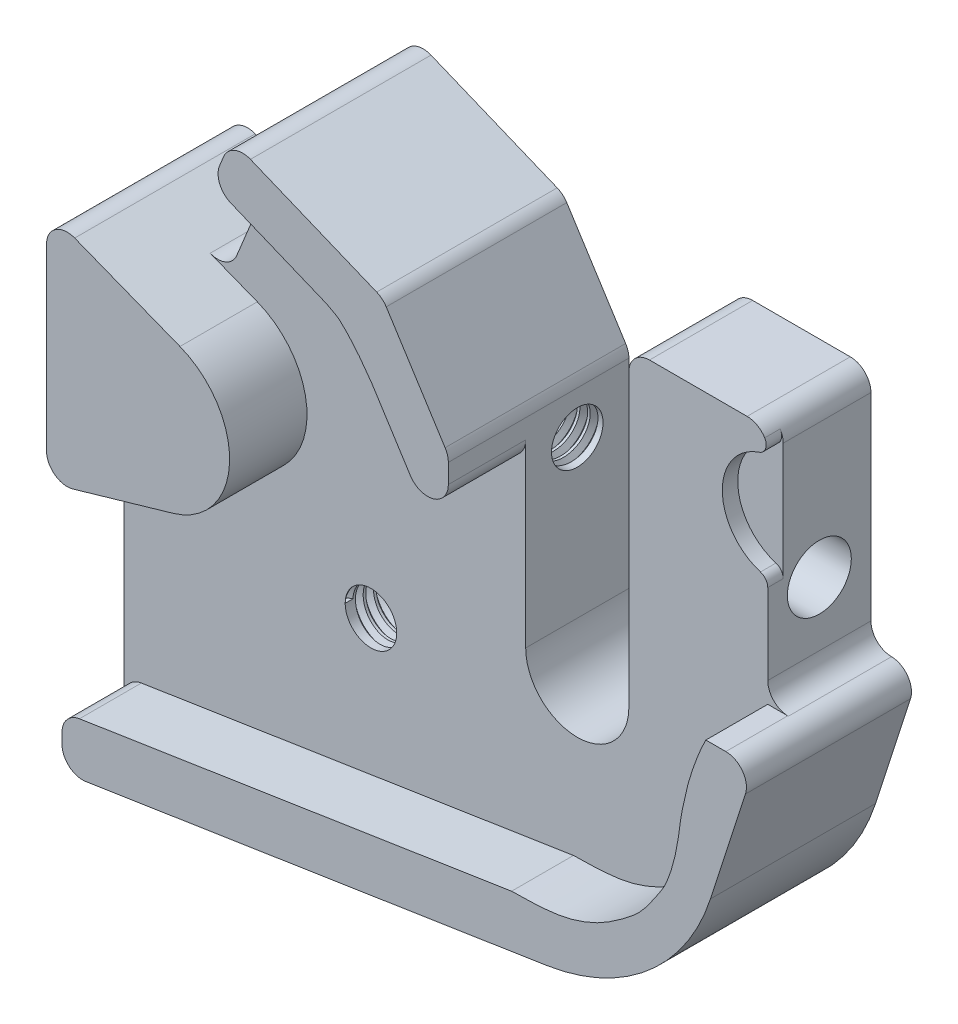
SolidWorks part; units mm, degrees
ref_plane "Front Plane" through (0, 0, 0) normal (0, 0, 1) x (1, 0, 0)
ref_plane "Top Plane" through (0, 0, 0) normal (0, 1, 0) x (1, 0, 0)
ref_plane "Right Plane" through (0, 0, 0) normal (1, 0, 0) x (0, 0, -1)
sketch "Sketch1" plane through (0, 0, 0) normal (0, 0, 1) x (1, 0, 0)
  line L0 (169.0465, 531.5792) -> (1384.9618, 942.3347) construction
  line L1 (17.1755, 0.269) -> (145.8355, -18.3486) construction
  line L2 (78.9683, 43.5936) -> (88.9683, 43.5936)
  line L3 (88.9683, 43.5936) -> (88.9683, 26.5936)
  line L4 (88.9683, 26.5936) -> (78.9683, 26.5936)
  line L5 (78.9683, 26.5936) -> (78.9683, 43.5936)
  line L6 (77.9414, 43.8024) -> (71.5407, 53.8656)
  line L7 (56.0381, 62.9033) -> (67.1668, 58.333)
  line L8 (88.9683, 43.5936) -> (88.9683, 61.7655)
  line L9 (88.9683, 61.7655) -> (102.4319, 61.7655)
  line L10 (77.9414, 43.8024) -> (78.9683, 42.1878)
  line L11 (20.6229, 24.1202) -> (53.1029, 33.5417)
  line L12 (23.9133, 59.0209) -> (55.1963, 46.7648)
  line L13 (56.0381, 62.9033) -> (50.2123, 48.7174)
  line L14 (70.3698, 62.4229) -> (72.6084, 61.5036)
  line L15 (20.6228, 1.7046) -> (20.6229, 24.1202)
  line L16 (20.6229, 24.1202) -> (20.6229, 30.1202)
  line L17 (103.2745, 61.7655) -> (102.4319, 61.7655)
  line L18 (20.6229, 30.1202) -> (43.6301, 36.7939)
  line L19 (23.9133, 59.0209) -> (22.0894, 54.3655)
  line L20 (22.0894, 54.3655) -> (44.4958, 45.587)
  line L21 (78.9683, 43.5936) -> (78.9683, 49.4415)
  line L22 (57.9376, 67.5285) -> (70.3698, 62.4229)
  line L23 (83.9683, 38.5936) -> (107.1142, 38.5936)
  line L24 (40.0198, 35.7467) -> (40.0198, 47.3406)
  line L25 (40.0198, 47.3406) -> (40.0198, 52.7107)
  line L26 (56.0381, 62.9033) -> (57.9376, 67.5285)
  line L27 (103.4635, 40.5809) -> (107.7563, 40.5809) construction
  line L28 (40.0198, 35.7467) -> (40.0198, 4.6997)
  line L29 (107.7563, 40.5809) -> (99.1103, 13.8239)
  line L30 (102.4319, 61.7655) -> (102.4319, 40.5809)
  line L31 (99.1103, 13.8239) -> (20.6228, 1.7046)
  line L32 (83.9683, 43.5936) -> (83.9683, 46.6936)
  line L33 (20.6228, 6.4639) -> (20.6228, 6.7639)
  line L34 (20.6228, 6.7639) -> (83.6, 16.4882)
  line L35 (20.6229, 30.1202) -> (20.6229, 61.7655)
  line L36 (23.9133, 59.0209) -> (20.6229, 60.3101)
  line L37 (22.0894, 54.3655) -> (20.6229, 54.94)
  line L38 (73.7743, 50.3539) -> (77.9932, 53.0374) construction
  line L39 (77.9932, 53.0374) -> (71.1704, 63.7644)
  line L40 (77.9932, 53.0374) -> (78.9683, 51.5043)
  line L41 (78.9683, 51.5043) -> (78.9683, 49.4415)
  line L42 (102.4319, 40.5809) -> (102.4319, 38.5936)
  line L47 (102.4319, 40.5809) -> (103.4635, 40.5809) construction
  circle A0 centre (83.9683, 31.5936) radius 5
  circle A1 centre (83.9683, 38.5936) radius 5
  circle A5 centre (50.1903, 40.5872) radius 7.578
  circle A6 centre (103.2745, 54.3655) radius 4.4
  circle A7 centre (103.2745, 54.3655) radius 7.4
  circle A8 centre (83.9683, 31.5936) radius 19.8723
  spline S0 degree 3 poles (67.1668, 58.333) (67.5307, 58.1482) (68.2163, 57.8297) (69.7375, 56.3376) (70.7671, 54.998) (71.5407, 53.8656) knots 0 0 0 0 0.194176 0.353383 1 1 1 1
  spline S1 degree 3 poles (83.6, 16.4882) (85.4172, 16.5376) (87.878, 16.5192) (90.6726, 17.4205) (92.3949, 18.1773) (94.0998, 19.3373) (95.7619, 20.5842) (96.8381, 21.8934) (97.5722, 23.0215) (98.2993, 24.0127) (98.8168, 25.1807) (99.3382, 26.7948) (99.7545, 28.7331) (99.9792, 30.8782) (100.4112, 32.873) (100.8434, 34.6928) (101.4168, 36.2088) (101.8572, 37.4461) (102.3579, 38.4137) (102.8415, 39.4999) (103.165, 40.2018) (103.4635, 40.5809) knots 0 0 0 0 0.157684 0.206761 0.251698 0.319001 0.383658 0.429514 0.463788 0.499543 0.534878 0.573031 0.645405 0.704849 0.75836 0.820852 0.865423 0.897677 0.933689 0.958942 1 1 1 1
  spline S2 degree 3 poles (103.4635, 40.5809) (103.5281, 40.7021) (103.6539, 40.9177) (103.7777, 41.1891) (104.0324, 41.5752) (104.2845, 42.0418) (104.6133, 42.6639) (105.0506, 43.3284) (105.5376, 44.1633) (106.1189, 44.9679) (106.7473, 45.8247) (107.3304, 46.576) (107.8594, 47.2965) (108.3783, 47.8664) (108.8492, 48.4246) (109.2415, 48.9281) (109.5877, 49.4941) (110.1609, 50.7988) (110.3782, 52.0409) (110.5419, 52.9707) knots 0 0 0 0 0.032133 0.040138 0.080049 0.114202 0.15475 0.224504 0.279876 0.355143 0.430433 0.500504 0.552615 0.615873 0.660356 0.704255 0.748281 0.797656 1 1 1 1
  dimension "D7" = 5
  dimension "D5" = 8.8
  dimension "D6" = 14.8
  dimension "D1" = 130
  dimension "D2" = 10
  dimension "D3" = 17
  dimension "D4" = 81.222
  dimension "D8" = 5
  dimension "D9" = 5
  dimension "D10" = 5
extrude "Main body" add sketch "Sketch1" along normal blind 10 contours L34 S1 A8 L47 L30 L8 L3 L4 L5 L10 L6 | S0 L7 L13 L12 A5 L11 L28 L34 A8 L6 | A0 L5 L4 | A0 L4 L3 | A8 L30 A7 L9 L8 | L30 A7 | L30 A8 L8 L3 L23 L42 | L30 A6 region at (78.4544, 40.3907, 0) region at (94.2116, 43.3445, 0) region at (94.7009, 53.6895, 0) region at (87.8514, 27.7104, 0) region at (80.0851, 27.7104, 0) region at (56.8317, 32.873, 0) region at (102.2709, 60.2007, 0) region at (100.9442, 54.3655, 0)
extrude "Top brackets" add sketch "Sketch1<3>" along normal blind 17.5 contours L7 S0 L6 A8 L41 L40 L39 L14 L22 L26 | L41 A8 L6 L10 L5 L21 | A5 | A5 L12 L25 L20 | A5 L20 L24 L18 | A5 L18 L28 L11 region at (77.485, 47.4328, 0) region at (68.2303, 59.1792, 0) region at (43.4702, 33.1986, 0) region at (43.8977, 48.9301, 0) region at (50.1903, 40.5872, 0) region at (41.5617, 41.668, 0)
sketch "Sketch1<3>" plane through (0, 0, 0) normal (0, 0, 1) x (1, 0, 0) same geometry as "Sketch1"
extrude "Bottom bracket" add sketch "Sketch1<4>" along normal blind 16 contours A8 L29 L23 | S1 L34 A8 L23 | A8 L34 L28 L31 region at (102.4994, 38.1861, 0) region at (104.6837, 35.2862, 0) region at (58.9948, 10.0364, 0)
sketch "Sketch1<4>" plane through (0, 0, 0) normal (0, 0, 1) x (1, 0, 0) same geometry as "Sketch1"
sketch "Sketch4" plane through (88.9683, 0, 0) normal (-1, 0, 0) x (0, 0, 1)
  line L0 (5, 61.7655) -> (5, 46.7655)
  line L2 (10, 61.7655) -> (0, 61.7655) construction
  circle A0 centre (5, 46.7655) radius 3.1
  dimension "D1" = 15
  dimension "D2" = 6.2
extrude "M6 axle tightening hole" cut sketch "Sketch4" against normal blind 30 contours A0 region at (88.9683, 44.6354, 2.87)
hole_wizard "M6 axle tightening tap" positions "3DSketch7" profile "Sketch10" hole size "M6x1.0" standard "ANSI Metric"
sketch3d "3DSketch7"
  line L0 (102.4319, 46.7655, 5) -> (88.9683, 46.7655, 5) construction
  point P0 (88.9683, 46.7655, 5)
sketch "Sketch10" plane through (88.9683, 46.7655, 5) normal (0, 1, 0) x (0, 0, -1)
  line L0 (0, 0) -> (0, 31.5022)
  line L1 (0, 31.5022) -> (2.5, 30)
  line L2 (2.5, 30) -> (2.5, 0)
  line L5 (2.5, 0) -> (0, 0)
  line L10 (0, 31.5022) -> (-2.5, 30) construction
  line L11 (0, -6.35) -> (0, 107.95) construction
  dimension "Hole Dia." = 5
  dimension "Hole Depth" = 30
  dimension "Drill Angle" = 118
thread "M6 axle tightening thread" pitch 1 method cut profile "Thread Profile2" start angle 0, offset 0, length 20, pitch 1, diameter 5
ref_plane "Plane2" through (78.9683, 46.7655, 7.5) normal (0, -1, 0) x (0, 0, 1)
sketch "Thread Profile2" plane through (78.9683, 46.7655, 7.5) normal (0, -1, 0) x (0, 0, 1)
  line L0 (0, 0) -> (0, 1) construction
  line L1 (0, 0) -> (0.5413, 0.3125)
  line L2 (0.5413, 0.3125) -> (0.5413, 0.4375)
  line L3 (0.5413, 0.4375) -> (0, 0.75)
  line L4 (0.5413, 0.375) -> (0, 0.375) construction
  line L11 (0, 0) -> (0, 0.75)
  point P2 (0, 0)
  dimension "Pitch" = 1
  dimension "Profile_Angle" = 60
  dimension "Profile_Land" = 0.125
  dimension "Profile_Height" = 0.5413
sketch "Frame lock position" plane through (0, 0, 10) normal (0, 0, 1) x (1, 0, 0)
  line L0 (83.9683, 26.5936) -> (63.9683, 26.5936)
  arc A0 (78.9683, 31.5936) -> (88.9683, 31.5936) centre (83.9683, 31.5936) ccw construction
hole_wizard "Frame lock tap" positions "3DSketch11" profile "Sketch15" hole size "M6x1.0" standard "ANSI Metric"
sketch3d "3DSketch11"
  point P0 (63.9683, 26.5936, 10)
sketch "Sketch15" plane through (63.9683, 26.5936, 10) normal (1, 0, 0) x (0, -1, 0)
  line L0 (0, 0) -> (0, 31.5022)
  line L1 (0, 31.5022) -> (2.5, 30)
  line L2 (2.5, 30) -> (2.5, 0)
  line L5 (2.5, 0) -> (0, 0)
  line L10 (0, 31.5022) -> (-2.5, 30) construction
  line L11 (0, -6.35) -> (0, 107.95) construction
  dimension "Hole Dia." = 5
  dimension "Hole Depth" = 30
  dimension "Drill Angle" = 118
thread "Frame lock thread" pitch 1 method cut profile "Thread Profile3" start angle 0, offset 0, length 20, pitch 1, diameter 5
ref_plane "Plane3" through (61.4683, 26.5936, 10) normal (0, -1, 0) x (-1, 0, 0)
sketch "Thread Profile3" plane through (61.4683, 26.5936, 10) normal (0, -1, 0) x (-1, 0, 0)
  line L0 (0, 0) -> (0, 1) construction
  line L1 (0, 0) -> (0.5413, 0.3125)
  line L2 (0.5413, 0.3125) -> (0.5413, 0.4375)
  line L3 (0.5413, 0.4375) -> (0, 0.75)
  line L4 (0.5413, 0.375) -> (0, 0.375) construction
  line L11 (0, 0) -> (0, 0.75)
  point P2 (0, 0)
  dimension "Pitch" = 1
  dimension "Profile_Angle" = 60
  dimension "Profile_Land" = 0.125
  dimension "Profile_Height" = 0.5413
fillet "2mm main fillets" radius 2 13 edges at (102.4319, 61.7655, 5) (88.9683, 61.7655, 5) (57.9376, 67.5285, 8.75) (56.0381, 62.9033, 13.75) (78.9683, 42.1878, 13.75) (50.2123, 48.7174, 5) (40.0198, 29.7467, 13.75) (40.0198, 52.7107, 8.75) (72.6084, 61.5036, 8.75) (40.0198, 4.6997, 8) (40.0198, 9.759, 13) (102.4319, 38.5936, 5) (78.9683, 51.5043, 8.75)
fillet "2mm extra fillet" radius 2 1 edges at (107.1142, 38.5936, 8)
sketch "Sketch16" plane through (0, 0, 10) normal (0, 0, 1) x (1, 0, 0)
  line L0 (78.9683, 43.5936) -> (88.9683, 43.5936)
  line L1 (88.9683, 43.5936) -> (88.9683, 26.5936)
  line L2 (88.9683, 26.5936) -> (78.9683, 26.5936)
  line L3 (78.9683, 26.5936) -> (78.9683, 43.5936)
  line L4 (77.9414, 43.8024) -> (71.5407, 53.8656)
  line L5 (56.0381, 62.9033) -> (67.1668, 58.333)
  line L6 (88.9683, 43.5936) -> (88.9683, 61.7655)
  line L7 (88.9683, 61.7655) -> (102.4319, 61.7655)
  line L8 (77.9414, 43.8024) -> (78.9683, 42.1878)
  line L9 (20.6229, 24.1202) -> (53.1029, 33.5417)
  line L10 (23.9133, 59.0209) -> (55.1963, 46.7648)
  line L11 (56.0381, 62.9033) -> (50.2123, 48.7174)
  line L12 (70.5008, 62.7543) -> (72.231, 62.0968)
  line L13 (20.6228, 1.7639) -> (20.6229, 24.1202)
  line L14 (20.6229, 24.1202) -> (20.6229, 30.1202)
  line L15 (103.2745, 61.7655) -> (102.4319, 61.7655)
  line L16 (20.6229, 30.1202) -> (43.6301, 36.7939)
  line L17 (23.9133, 59.0209) -> (22.0894, 54.3655)
  line L18 (22.0894, 54.3655) -> (44.4958, 45.587)
  line L19 (78.9683, 43.5936) -> (78.9683, 49.4415)
  line L20 (57.9376, 67.5285) -> (70.5008, 62.7543)
  line L21 (83.9683, 38.5936) -> (107.6777, 38.5936)
  line L22 (40.0198, 35.7467) -> (40.0198, 47.3406)
  line L23 (40.0198, 47.3406) -> (40.0198, 52.7107)
  line L24 (56.0381, 62.9033) -> (57.9376, 67.5285)
  line L25 (103.4635, 40.5809) -> (108.336, 40.5809) construction
  line L26 (40.0198, 35.7467) -> (40.0198, 4.6135)
  line L27 (108.336, 40.5809) -> (99.307, 13.3233)
  line L28 (102.4319, 61.7655) -> (102.4319, 40.5809)
  line L29 (99.307, 13.3233) -> (20.6228, 1.7639)
  line L30 (83.9683, 43.5936) -> (83.9683, 46.6936)
  line L31 (20.6228, 6.4639) -> (20.6228, 6.7639)
  line L32 (20.6228, 6.7639) -> (83.6, 16.4882)
  line L33 (20.6229, 30.1202) -> (20.6229, 61.7655)
  line L34 (23.9133, 59.0209) -> (20.6229, 60.3101)
  line L35 (22.0894, 54.3655) -> (20.6229, 54.94)
  line L36 (73.7743, 50.3539) -> (77.9932, 53.0374) construction
  line L37 (77.9932, 53.0374) -> (71.1704, 63.7644)
  line L38 (77.9932, 53.0374) -> (78.9683, 51.5043)
  line L39 (78.9683, 51.5043) -> (78.9683, 49.4415)
  line L40 (102.4319, 40.5809) -> (102.4319, 38.5936)
  line L41 (102.4319, 40.5809) -> (103.4635, 40.5809) construction
  circle A0 centre (83.9683, 31.5936) radius 5
  circle A1 centre (83.9683, 38.5936) radius 5
  circle A2 centre (50.1903, 40.5872) radius 7.578
  circle A3 centre (103.2745, 54.3655) radius 4.4
  circle A4 centre (103.2745, 54.3655) radius 7.4
  circle A5 centre (83.9683, 31.5936) radius 20.3057
  circle A6 centre (103.2745, 54.3655) radius 5.25
  spline S0 degree 3 poles (67.1668, 58.333) (67.5307, 58.1482) (68.2163, 57.8297) (69.7375, 56.3376) (70.7671, 54.998) (71.5407, 53.8656) knots 0 0 0 0 0.194176 0.353383 1 1 1 1
  spline S1 degree 3 poles (83.6, 16.4882) (85.4172, 16.5376) (87.878, 16.5192) (90.6726, 17.4205) (92.3949, 18.1773) (94.0998, 19.3373) (95.7619, 20.5842) (96.8381, 21.8934) (97.5722, 23.0215) (98.2993, 24.0127) (98.8168, 25.1807) (99.3382, 26.7948) (99.7545, 28.7331) (99.9792, 30.8782) (100.4112, 32.873) (100.8434, 34.6928) (101.4168, 36.2088) (101.8572, 37.4461) (102.3579, 38.4137) (102.8415, 39.4999) (103.165, 40.2018) (103.4635, 40.5809) knots 0 0 0 0 0.157684 0.206761 0.251698 0.319001 0.383658 0.429514 0.463788 0.499543 0.534878 0.573031 0.645405 0.704849 0.75836 0.820852 0.865423 0.897677 0.933689 0.958942 1 1 1 1
  spline S2 degree 3 poles (103.4635, 40.5809) (103.5281, 40.7021) (103.6539, 40.9177) (103.7777, 41.1891) (104.0324, 41.5752) (104.2845, 42.0418) (104.6133, 42.6639) (105.0506, 43.3284) (105.5376, 44.1633) (106.1189, 44.9679) (106.7473, 45.8247) (107.3304, 46.576) (107.8594, 47.2965) (108.3783, 47.8664) (108.8492, 48.4246) (109.2415, 48.9281) (109.5877, 49.4941) (110.1609, 50.7988) (110.3782, 52.0409) (110.5419, 52.9707) knots 0 0 0 0 0.032133 0.040138 0.080049 0.114202 0.15475 0.224504 0.279876 0.355143 0.430433 0.500504 0.552615 0.615873 0.660356 0.704255 0.748281 0.797656 1 1 1 1
  dimension "D3" = 8.8
  dimension "D4" = 14.8
  dimension "D9" = 10.5
  dimension "D1" = 10
  dimension "D2" = 17
  dimension "D5" = 5
  dimension "D6" = 5
  dimension "D7" = 5
  dimension "D8" = 5
extrude "Derailleur screw cutout" cut sketch "Sketch16" against normal blind 1.5 contours A6
fillet "1mm fillets" radius 1 2 edges at (102.4319, 49.1835, 9.25) (102.4319, 59.5474, 9.25)
